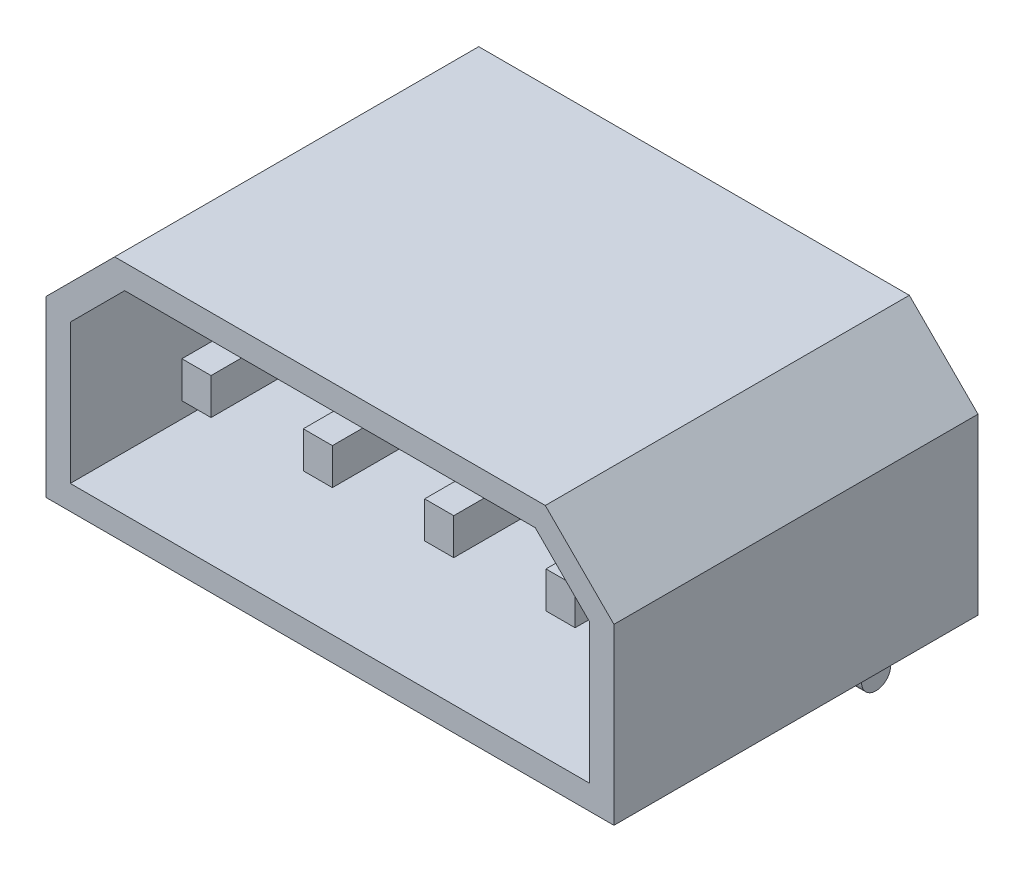
SolidWorks part; units mm, degrees
ref_plane "Front" through (0, 0, 0) normal (0, 0, 1) x (1, 0, 0)
ref_plane "Top" through (0, 0, 0) normal (0, 1, 0) x (1, 0, 0)
ref_plane "Right" through (0, 0, 0) normal (1, 0, 0) x (0, 0, -1)
sketch "Sketch1" plane through (0, 0, 0) normal (0, 0, 1) x (1, 0, 0)
  line L0 (0, 0) -> (2.1, 0) construction
  line L1 (2.1, 0) -> (4.6, 0) construction
  line L2 (4.6, 0) -> (7.1, 0) construction
  line L3 (7.1, 0) -> (9.6, 0) construction
  line L4 (9.6, 0) -> (11.7, 0) construction
  line L5 (0, 0) -> (11.7, 0)
  line L6 (11.7, 0) -> (11.7, 3.5858)
  line L7 (11.7, 3.5858) -> (10.2858, 5)
  line L8 (10.2858, 5) -> (1.4142, 5)
  line L9 (1.4142, 5) -> (0, 3.5858)
  line L10 (0, 3.5858) -> (0, 0)
  line L11 (1.4142, 5) -> (0, 5) construction
  line L12 (0, 5) -> (0, 3.5858) construction
  dimension "D1" = 2.5
  dimension "D2" = 2.1
  dimension "D3" = 45
  dimension "D4" = 5
  dimension "D5" = 2
extrude "Extrude-Thin1" add sketch "Sketch1" along normal blind 7.5 thin thin type one direction reverse wall 0.5
sketch "Sketch2" plane through (0, 0, 0) normal (0, 0, -1) x (-1, 0, 0)
  line L6 (0, 0) -> (0, 3.5858)
  line L7 (0, 3.5858) -> (-1.4142, 5)
  line L8 (-1.4142, 5) -> (-10.2858, 5)
  line L9 (-10.2858, 5) -> (-11.7, 3.5858)
  line L10 (-11.7, 3.5858) -> (-11.7, 0)
  line L11 (-11.7, 0) -> (0, 0)
  line L12 (0, 0) -> (0, 3.5858)
  line L13 (0, 3.5858) -> (-1.4142, 5)
  line L14 (-1.4142, 5) -> (-10.2858, 5)
  line L15 (-10.2858, 5) -> (-11.7, 3.5858)
  line L16 (-11.7, 3.5858) -> (-11.7, 0)
  line L17 (-11.7, 0) -> (0, 0)
  dimension "D1" = 0
extrude "Boss-Extrude1" add sketch "Sketch2" against normal blind 3
ref_plane "Plane1" through (9.6, 0, 0) normal (1, 0, 0) x (0, 0, -1)
sketch "Sketch3" plane through (9.6, 0, 0) normal (1, 0, 0) x (0, 0, -1)
  line L0 (-6.5, 2.875) -> (0, 2.875)
  line L1 (0, 2.875) -> (0, -1.8)
  line L2 (-0.6, -1.8) -> (-0.6, 2.125)
  line L3 (-0.6, 2.125) -> (-6.5, 2.125)
  line L4 (-6.5, 2.125) -> (-6.5, 2.875)
  line L5 (-7.5, 4.5) -> (-3, 4.5) construction
  line L6 (-7.5, 4.5) -> (-3, 4.5) construction
  line L7 (-7.5, 0.5) -> (-3, 0.5) construction
  line L8 (-7.5, 0.5) -> (-3, 0.5) construction
  line L9 (-3, 4.5) -> (-3, 0.5) construction
  line L10 (-7.5, 0) -> (0, 0) construction
  line L11 (-7.5, 0) -> (0, 0) construction
  line L12 (-0.3, -2.1) -> (-2.2249, -2.1) construction
  line L13 (0, 3.5858) -> (0, 0) construction
  line L14 (0, 3.5858) -> (0, 0) construction
  line L15 (-6.5, 2.5) -> (-3, 2.5) construction
  line L16 (-7.5, 4.5) -> (-7.5, 0.5) construction
  arc A0 (0, -1.8) -> (-0.6, -1.8) centre (-0.3, -1.8) cw
  dimension "D1" = 0.6
  dimension "D2" = 0.75
  dimension "D3" = 2.1
  dimension "D4" = 1
extrude "Boss-Extrude2" add sketch "Sketch3" along normal mid plane 0.6
pattern_linear "LPattern1" count 4 spacing 2.5 along (-1, 0, 0) of "Boss-Extrude2"
sketch "Sketch4" plane through (0, 0, 0) normal (0, -1, 0) x (1, 0, 0)
  line L0 (9.9, 0) -> (9.9, 0.6) construction
  line L1 (9.9, 0) -> (9.3, 0) construction
  line L2 (9.9, 0.6) -> (9.3, 0.6) construction
  line L3 (9.3, 0) -> (9.3, 0.6) construction
  line L4 (9.9, 0) -> (9.9, 0.6)
  line L5 (9.9, 0) -> (9.3, 0)
  line L6 (9.9, 0.6) -> (9.3, 0.6)
  line L7 (9.3, 0) -> (9.3, 0.6)
  line L8 (9.6, 0) -> (9.6, 0.6) construction
  point P6 (9.6, 0.3)
ref_axis "Axis1" through (9.6, 0, 0.3) along (0, -1, 0)
ref_plane "Plane2" through (5.85, 0, 0) normal (-1, 0, 0) x (0, 0, 1)
